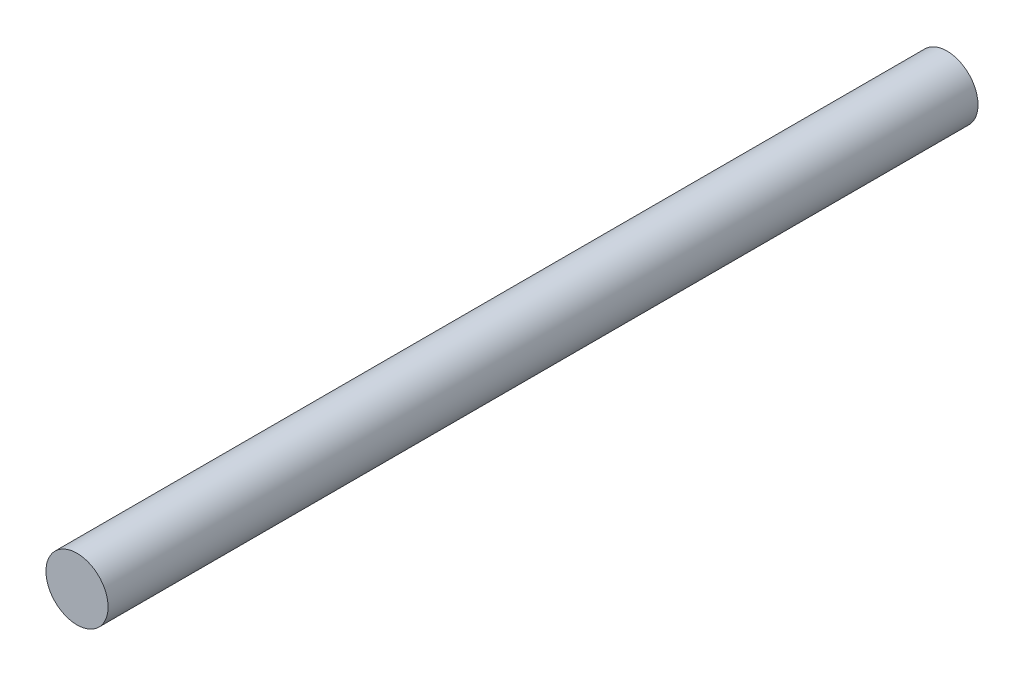
SolidWorks part; units mm, degrees
material "ABS"
ref_plane "Front Plane" through (0, 0, 0) normal (0, 0, 1) x (1, 0, 0)
ref_plane "Top Plane" through (0, 0, 0) normal (0, 1, 0) x (1, 0, 0)
ref_plane "Right Plane" through (0, 0, 0) normal (1, 0, 0) x (0, 0, -1)
sketch "Sketch1" plane through (0, 0, 0) normal (0, 0, 1) x (1, 0, 0)
  circle A0 centre (0, 0) radius 2.5
  dimension "D1" = 5
extrude "Boss-Extrude1" add sketch "Sketch1" along normal mid plane 70
